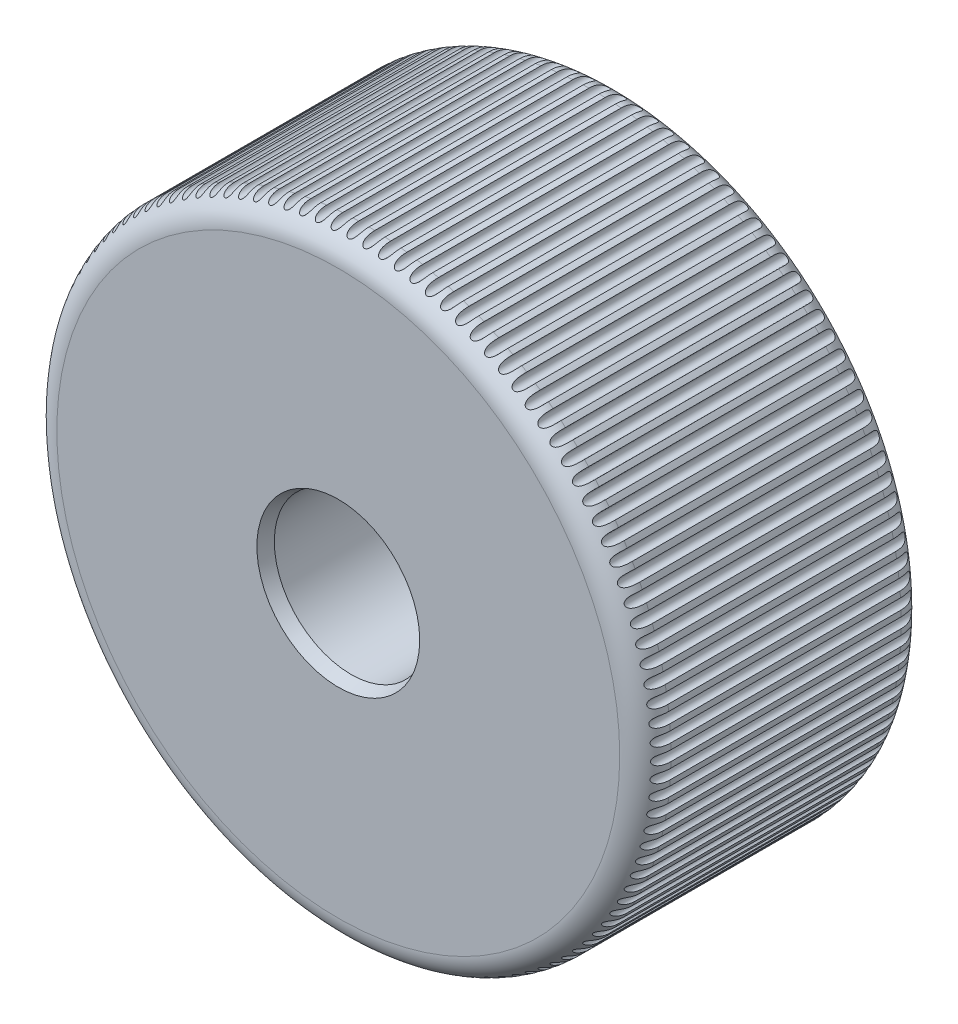
SolidWorks part; units mm, degrees
ref_plane "Спереди" through (0, 0, 0) normal (0, 0, 1) x (1, 0, 0)
ref_plane "Сверху" through (0, 0, 0) normal (0, 1, 0) x (1, 0, 0)
ref_plane "Справа" through (0, 0, 0) normal (1, 0, 0) x (0, 0, -1)
sketch "Эскиз1" plane through (0, 0, 0) normal (0, 0, 1) x (1, 0, 0)
  line L0 (-2.9394, 0.6) -> (2.9394, 0.6)
  line L1 (-2.9394, -0.6) -> (2.9394, -0.6)
  circle A0 centre (0, 0) radius 3
  circle A1 centre (0, 0) radius 12
  dimension "D1" = 6
  dimension "D4" = 24
  dimension "D2" = 1.2
  dimension "D3" = 0.6
extrude "Бобышка-Вытянуть1" add sketch "Эскиз1" along normal blind 11 contours A1 A0 region at (-11.6606, 0, 0)
extrude "Бобышка-Вытянуть2" add sketch "Эскиз1<3>" along normal blind 2 contours L0 A0 | L0 A0 L1 | L1 A0 region at (0, 1.6031, 0) region at (0, 0, 0) region at (0, -1.6031, 0)
sketch "Эскиз1<3>" plane through (0, 0, 0) normal (0, 0, 1) x (1, 0, 0) same geometry as "Эскиз1"
extrude "Бобышка-Вытянуть3" add sketch "Эскиз1<4>" along normal blind 6 contours L0 A0 L1 region at (0, 0, 0)
sketch "Эскиз1<4>" plane through (0, 0, 0) normal (0, 0, 1) x (1, 0, 0) same geometry as "Эскиз1"
chamfer "Фаска1" distance 4 angle 3 1 edges at (0, 0.6, 6) first distance on face at (0, 0.6, 4)
chamfer "Фаска2" distance 4 angle 3 1 edges at (0, -0.6, 6) first distance on face at (0, -0.6, 4)
fillet "Скругление1" radius 1 2 edges at (12, 0, 0) (12, 0, 11)
chamfer "Фаска3" distance 0.5 angle 20 1 edges at (3, 0, 11) first distance on face at (0, 0, 3.997)
sketch "Эскиз2" plane through (0, 0, 11) normal (0, 0, 1) x (1, 0, 0)
  circle A0 centre (0, 0) radius 12
  circle A1 centre (0, 12) radius 0.2
  dimension "D1" = 0.4
extrude "Вырез-Вытянуть2" cut sketch "Эскиз2" against normal through all both and the other way through all contours A1
pattern_circular "Круговой массив1" count 120 every 3 about axis through (0, 0, 10) along (0, 0, -1) of "Вырез-Вытянуть2"
